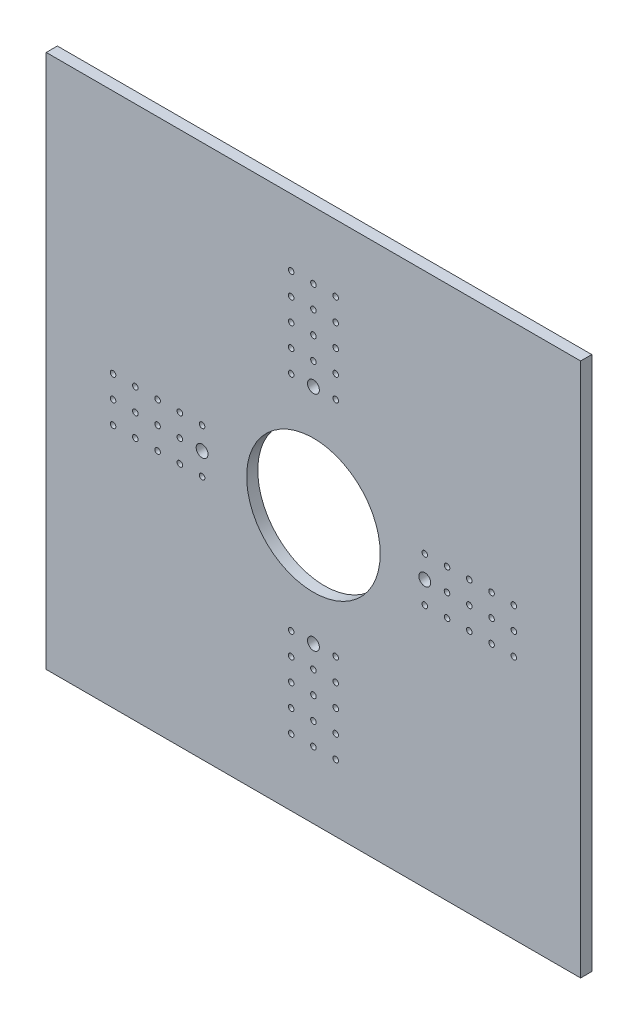
SolidWorks part; units mm, degrees
material "AISI 1020"
ref_plane "Front Plane" through (0, 0, 0) normal (0, 0, 1) x (1, 0, 0)
ref_plane "Top Plane" through (0, 0, 0) normal (0, 1, 0) x (1, 0, 0)
ref_plane "Right Plane" through (0, 0, 0) normal (1, 0, 0) x (0, 0, -1)
sketch "Sketch1" plane through (0, 0, 0) normal (0, 0, 1) x (1, 0, 0)
  line L5 (-304.8, -304.8) -> (304.8, -304.8)
  line L6 (-304.8, -304.8) -> (-304.8, 304.8)
  line L7 (-304.8, 304.8) -> (304.8, 304.8)
  line L8 (304.8, -304.8) -> (304.8, 304.8)
  line L9 (-304.8, -304.8) -> (304.8, 304.8) construction
  line L10 (-304.8, 304.8) -> (304.8, -304.8) construction
  circle A0 centre (0, 0) radius 76.2
  dimension "D2" = 152.4
  dimension "D1" = 609.6
extrude "Boss-Extrude1" add sketch "Sketch1" against normal blind 12.7
sketch "Sketch3" plane through (0, 0, 0) normal (0, 0, 1) x (1, 0, 0)
  line L0 (0, 0) -> (-127, 0) construction
  line L1 (-127, 25.4) -> (-127, -25.4) construction
  circle A0 centre (-127, 0) radius 3.175
  circle A1 centre (-127, 25.4) radius 3.175
  circle A2 centre (-127, -25.4) radius 3.175
  point P8 (-127, 0)
  dimension "D2" = 6.35
  dimension "D1" = 127
  dimension "D3" = 50.8
extrude "Cut-Extrude1" cut sketch "Sketch3" against normal up to next
pattern_linear "LPattern1" count 5 spacing 25.4 along (-1, 0, 0) of "Cut-Extrude1"
pattern_circular "CirPattern1" count 4 over 360 about axis through (0, 0, -12.7) along (0, 0, 1) of "LPattern1", "Cut-Extrude1"
sketch "Sketch4" plane through (0, 0, 0) normal (0, 0, 1) x (1, 0, 0)
  circle A0 centre (-127, 0) radius 6.7577
  dimension "D1" = 13.5153
extrude "Cut-Extrude2" cut sketch "Sketch4" against normal up to next
pattern_circular "CirPattern2" count 4 over 360 about axis through (0, 0, -12.7) along (0, 0, 1) of "Cut-Extrude2"
